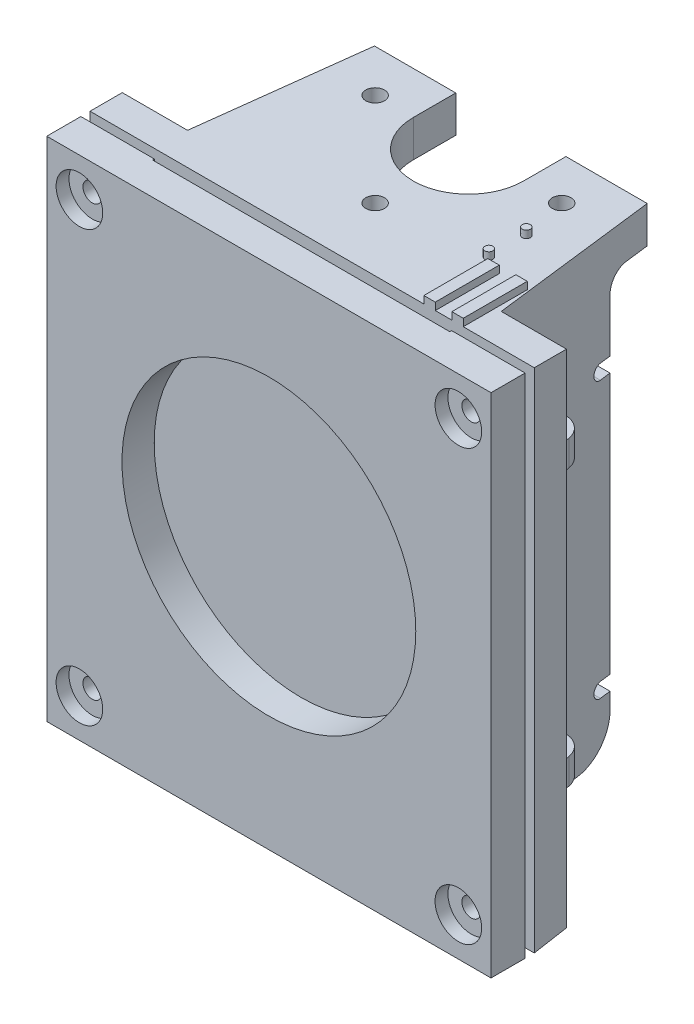
SolidWorks part; units mm, degrees
ref_plane "Front Plane" through (0, 0, 0) normal (0, 0, 1) x (1, 0, 0)
ref_plane "Top Plane" through (0, 0, 0) normal (0, 1, 0) x (1, 0, 0)
ref_plane "Right Plane" through (0, 0, 0) normal (1, 0, 0) x (0, 0, -1)
sketch "Sketch1" plane through (0, 0, 0) normal (0, 1, 0) x (1, 0, 0)
  line L0 (-32.5572, 0) -> (-38.5572, 0)
  line L5 (-38.5572, 0) -> (-42.7047, -33.7788)
  line L7 (42.7047, -33.7788) -> (38.5572, 0)
  line L8 (38.5572, 0) -> (32.5572, 0)
  line L9 (-42.7047, -33.7788) -> (-60.4847, -33.7788)
  line L10 (-60.4847, -33.7788) -> (-60.4847, -42.5572)
  line L11 (-60.4847, -42.5572) -> (60.4847, -42.5572)
  line L12 (60.4847, -42.5572) -> (60.4847, -33.7788)
  line L13 (60.4847, -33.7788) -> (42.7047, -33.7788)
  line L14 (0, 0) -> (0, -32.5572) construction
  line L15 (38.5572, 0) -> (38.5572, -26.0046) construction
  line L16 (51.5947, -33.7788) -> (51.5947, -54.3356) construction
  line L17 (-60.4847, -45.5572) -> (60.4847, -45.5572)
  line L18 (-60.4847, -45.5572) -> (-60.4847, -54.3356)
  line L19 (-60.4847, -54.3356) -> (60.4847, -54.3356)
  line L20 (60.4847, -45.5572) -> (60.4847, -54.3356)
  line L21 (49.042, -33.7788) -> (49.042, -54.3356) construction
  line L23 (54.1474, -33.7788) -> (54.1474, -54.3356) construction
  line L26 (46.8322, -36.9538) -> (56.3572, -36.9538) construction
  line L27 (46.8322, -36.9538) -> (46.8322, -33.7788) construction
  line L28 (46.8322, -33.7788) -> (56.3572, -33.7788) construction
  line L29 (56.3572, -36.9538) -> (56.3572, -33.7788) construction
  line L30 (46.8322, -36.9538) -> (56.3572, -33.7788) construction
  line L31 (46.8322, -33.7788) -> (56.3572, -36.9538) construction
  line L32 (49.9992, -31.7788) -> (74.4903, -31.7788) construction
  line L33 (45.2447, -55.9088) -> (57.9447, -55.9088) construction
  line L34 (45.2447, -55.9088) -> (45.2447, -50.8288) construction
  line L35 (45.2447, -50.8288) -> (57.9447, -50.8288) construction
  line L36 (57.9447, -55.9088) -> (57.9447, -50.8288) construction
  line L37 (45.2447, -55.9088) -> (57.9447, -50.8288) construction
  line L38 (45.2447, -50.8288) -> (57.9447, -55.9088) construction
  circle A0 centre (0, 0) radius 32.5572 construction
  arc A1 (-32.5572, 0) -> (32.5572, 0) centre (0, 0) ccw
  point P27 (51.5947, -35.3663)
  point P32 (51.5947, -53.3688)
  point P44 (42.7047, -33.7788)
  point P47 (-42.7047, -33.7788)
  dimension "D1" = 65.1144
  dimension "D2" = 10
  dimension "D3" = 6
  dimension "D4" = 7
  dimension "D6" = 3
  dimension "D5" = 5.1054
  dimension "D7" = 9.525
  dimension "D8" = 3.175
  dimension "D9" = 2
  dimension "D11" = 12.7
  dimension "D12" = 5.08
  dimension "D13" = 2.54
  dimension "D10" = 19.05
  dimension "D14" = 5.6034
extrude "Boss-Extrude1" add sketch "Sketch1" along normal mid plane 113.03 contours A1 L8 L7 L13 L12 L11 L10 L9 L5 L0
sketch "Sketch4" plane through (0, -56.515, 0) normal (0, -1, 0) x (1, 0, 0)
  line L0 (-60.4847, 33.7788) -> (-60.4847, 42.5572) construction
  line L1 (60.4847, 42.5572) -> (-60.4847, 42.5572)
  line L2 (60.4847, 42.5572) -> (60.4847, 33.7788)
  line L4 (-60.4847, 42.5572) -> (-60.4847, 33.7788)
  line L5 (60.4847, 33.7788) -> (42.7047, 33.7788)
  line L6 (42.7047, 33.7788) -> (38.5572, 0) construction
  line L7 (42.7047, 33.7788) -> (40.399, 15)
  line L8 (40.399, 15) -> (-40.399, 15) construction
  line L9 (-38.5572, 0) -> (-42.7047, 33.7788) construction
  line L10 (-40.399, 15) -> (-42.7047, 33.7788)
  line L11 (-42.7047, 33.7788) -> (-60.4847, 33.7788)
  line L12 (40.399, 15) -> (13.2288, 15)
  line L13 (-40.399, 15) -> (-13.2288, 15)
  line L14 (-42.7047, 33.7788) -> (-60.4847, 33.7788) construction
  circle A0 centre (0, 0) radius 20 construction
  arc A1 (13.2288, 15) -> (-13.2288, 15) centre (0, 0) ccw
  arc A2 (32.5572, 0) -> (-32.5572, 0) centre (0, 0) ccw construction
  dimension "D2" = 40
  dimension "D3" = 15
extrude "Boss-Extrude2" add sketch "Sketch4" along normal blind 15
sketch "Sketch5" plane through (0, 56.515, 0) normal (0, 1, 0) x (1, 0, 0)
  line L0 (-42.7047, -33.7788) -> (-37.1387, 11.5527)
  line L1 (-60.4847, -42.5572) -> (60.4847, -42.5572)
  line L2 (-60.4847, -42.5572) -> (-60.4847, -33.7788)
  line L3 (-60.4847, -33.7788) -> (60.4847, -33.7788) construction
  line L4 (60.4847, -42.5572) -> (60.4847, -33.7788)
  line L5 (-37.1387, 11.5527) -> (-15, 11.5527)
  line L6 (37.1387, 11.5527) -> (42.7047, -33.7788)
  line L7 (-42.7047, -33.7788) -> (-60.4847, -33.7788) construction
  line L8 (42.7047, -33.7788) -> (38.5572, 0) construction
  line L9 (-38.5572, 0) -> (-42.7047, -33.7788) construction
  line L10 (-60.4847, -33.7788) -> (-42.7047, -33.7788)
  line L11 (42.7047, -33.7788) -> (60.4847, -33.7788)
  line L12 (-15, 11.5527) -> (-15, 0)
  line L13 (15, 11.5527) -> (15, 0)
  line L14 (15, 11.5527) -> (37.1387, 11.5527)
  line L15 (60.4847, -42.5572) -> (60.4847, -33.7788) construction
  circle A0 centre (0, 0) radius 25.4 construction
  circle A1 centre (0, -25.4) radius 2.5527
  circle A2 centre (25.4, 0) radius 2.5527
  circle A3 centre (-25.4, 0) radius 2.5527
  arc A4 (-15, 0) -> (15, 0) centre (0, 0) ccw
  dimension "D1" = 50.8
  dimension "D2" = 5.1054
  dimension "D3" = 15
  dimension "D4" = 9
extrude "Boss-Extrude3" add sketch "Sketch5" along normal blind 10
sketch "Sketch7" plane through (0, 0, 33.7788) normal (0, 0, -1) x (-1, 0, 0)
  line L0 (51.5947, 66.515) -> (51.5947, -71.515) construction
  line L1 (42.7047, 66.515) -> (60.4847, 66.515) construction
  line L2 (60.4847, -71.515) -> (42.7047, -71.515) construction
  line L3 (60.4847, -2.5) -> (-60.4847, -2.5) construction
  line L4 (60.4847, 66.515) -> (60.4847, -71.515) construction
  line L5 (-60.4847, 66.515) -> (-60.4847, -71.515) construction
  line L6 (46.8322, -58.2661) -> (51.5947, -55.5165)
  line L7 (51.5947, 50.5165) -> (56.3572, 53.2661)
  line L8 (56.3572, 53.2661) -> (56.3572, 58.7654)
  line L9 (56.3572, 58.7654) -> (51.5947, 61.515)
  line L10 (51.5947, 61.515) -> (46.8322, 58.7654)
  line L11 (46.8322, 58.7654) -> (46.8322, 53.2661)
  line L12 (46.8322, 53.2661) -> (51.5947, 50.5165)
  line L13 (46.8322, -63.7654) -> (46.8322, -58.2661)
  line L14 (51.5947, -66.515) -> (46.8322, -63.7654)
  line L15 (56.3572, -63.7654) -> (51.5947, -66.515)
  line L16 (56.3572, -58.2661) -> (56.3572, -63.7654)
  line L17 (51.5947, -55.5165) -> (56.3572, -58.2661)
  line L18 (0, 0) -> (0, -85.6539) construction
  line L19 (-51.5947, -55.5165) -> (-56.3572, -58.2661)
  line L20 (-56.3572, -58.2661) -> (-56.3572, -63.7654)
  line L21 (-56.3572, -63.7654) -> (-51.5947, -66.515)
  line L22 (-51.5947, -66.515) -> (-46.8322, -63.7654)
  line L23 (-46.8322, -63.7654) -> (-46.8322, -58.2661)
  line L24 (-46.8322, 53.2661) -> (-51.5947, 50.5165)
  line L25 (-46.8322, 58.7654) -> (-46.8322, 53.2661)
  line L26 (-51.5947, 61.515) -> (-46.8322, 58.7654)
  line L27 (-56.3572, 58.7654) -> (-51.5947, 61.515)
  line L28 (-56.3572, 53.2661) -> (-56.3572, 58.7654)
  line L29 (-51.5947, 50.5165) -> (-56.3572, 53.2661)
  line L30 (-46.8322, -58.2661) -> (-51.5947, -55.5165)
  circle A0 centre (51.5947, 56.0157) radius 4.7625 construction
  circle A1 centre (51.5947, -61.0157) radius 4.7625 construction
  circle A2 centre (-51.5947, -61.0157) radius 4.7625 construction
  circle A3 centre (-51.5947, 56.0157) radius 4.7625 construction
  dimension "D1" = 9.525
  dimension "D2" = 5
ref_plane "Plane1" through (0, 0, 36.9538) normal (0, 0, -1) x (-1, 0, 0)
extrude "Cut-Extrude1" cut sketch "Sketch7" against normal up to surface (3.175 mm away) up to plane "Plane1"
sketch "Sketch9" plane through (0, 0, 33.7788) normal (0, 0, -1) x (-1, 0, 0)
  circle A0 centre (51.5947, 56.0157) radius 2.5527
  circle A1 centre (51.5947, -61.0157) radius 2.5527
  circle A2 centre (-51.5947, -61.0157) radius 2.5527
  circle A3 centre (-51.5947, 56.0157) radius 2.5527
  dimension "D1" = 5.1054
extrude "Cut-Extrude2" cut sketch "Sketch9" against normal up to next
extrude "Boss-Extrude4" add sketch "Sketch1<3>" along normal up to surface and the other way up to surface separate body contours L19 L20 L17 L18 up to face at (25.4, 66.515, 2.5527) other way up to face at (0, -71.515, 28.523)
sketch "Sketch1<3>" plane through (0, 0, 0) normal (0, 1, 0) x (1, 0, 0) same geometry as "Sketch1"
sketch "Sketch10" plane through (0, 0, 54.3356) normal (0, 0, 1) x (1, 0, 0)
  circle A0 centre (-51.5947, 56.0157) radius 6.35
  circle A1 centre (51.5947, 56.0157) radius 6.35
  circle A2 centre (51.5947, -61.0157) radius 6.35
  circle A3 centre (-51.5947, -61.0157) radius 6.35
  dimension "D1" = 12.7
extrude "Cut-Extrude3" cut sketch "Sketch10" against normal up to vertex (3.5067 mm away) up to point (57.9447, 0, 50.8288)
sketch "Sketch11" plane through (0, 66.515, 0) normal (0, 1, 0) x (1, 0, 0)
  line L0 (-60.4847, -45.5572) -> (-60.4847, -45.0572)
  line L1 (-60.4847, -45.0572) -> (-40.4847, -45.0572)
  line L2 (-40.4847, -45.0572) -> (-40.4847, -45.5572)
  line L3 (-60.4847, -45.5572) -> (60.4847, -45.5572) construction
  line L4 (-40.4847, -45.5572) -> (-60.4847, -45.5572)
  line L5 (0, -45.5572) -> (0, -54.3356) construction
  line L6 (-60.4847, -54.3356) -> (60.4847, -54.3356) construction
  line L7 (40.4847, -45.5572) -> (60.4847, -45.5572)
  line L8 (40.4847, -45.0572) -> (40.4847, -45.5572)
  line L9 (60.4847, -45.0572) -> (40.4847, -45.0572)
  line L10 (60.4847, -45.5572) -> (60.4847, -45.0572)
  dimension "D1" = 0.5
  dimension "D2" = 20
extrude "Boss-Extrude5" add sketch "Sketch11" against normal up to surface (138.03 mm away) up to face at (0, -71.515, 49.9464)
extrude "Cut-Extrude4" cut sketch "Sketch9<2>" against normal through all both and the other way through all contours A1 | A2 | A3 | A0
sketch "Sketch9<2>" plane through (0, 0, 33.7788) normal (0, 0, -1) x (-1, 0, 0) same geometry as "Sketch9"
ref_plane "Plane2" through (0, -36.515, 0) normal (0, -1, 0) x (-1, 0, 0)
sketch "Sketch13" plane through (0, -36.515, 0) normal (0, -1, 0) x (-1, 0, 0)
  line L0 (0, 0) -> (0, -54.3356) construction
  line L1 (60.4847, -54.3356) -> (-60.4847, -54.3356) construction
  line L2 (-53.8496, -26.5153) -> (-56.6783, -42.5572)
  line L3 (-56.6783, -42.5572) -> (-41.9408, -42.5572)
  line L4 (-60.4847, -42.5572) -> (60.4847, -42.5572) construction
  line L5 (-41.9408, -42.5572) -> (-41.9408, -27.5572)
  line L7 (-40.399, -15) -> (-42.7047, -33.7788) construction
  circle A0 centre (-47.9408, -27.5572) radius 6 construction
  circle A1 centre (-47.9408, -27.5572) radius 2
  arc A2 (-53.8496, -26.5153) -> (-41.9408, -27.5572) centre (-47.9408, -27.5572) cw
  point P0 (-55.9726, -42.5572)
  dimension "D1" = 4
  dimension "D2" = 6
  dimension "D3" = 15
  dimension "D4" = 10
extrude "Boss-Extrude6" add sketch "Sketch13" along normal blind 7
mirror "Mirror1" about plane through (0, 0, 0) normal (1, 0, 0) of "Boss-Extrude6"
ref_plane "Plane3" through (0, -2.5, 0) normal (0, -1, 0) x (-1, 0, 0)
draft "Draft1" type of draft neutral plane draft angle 10 faces to draft 1 face at (0, -71.515, 28.523) neutral plane through (-60.4847, 56.515, 42.5572) neutral plane normal (0, 0, 1) reverse direction yes parameters "D1"=10
fillet "Fillet5" radius 1.3 4 edges at (-54.1474, 56.0157, 36.9538) (49.042, 56.0157, 36.9538) (49.042, -61.0157, 36.9538) (-54.1474, -61.0157, 36.9538)
sketch "Sketch16" plane through (0, 0, 54.3356) normal (0, 0, 1) x (1, 0, 0)
  circle A0 centre (0, 0) radius 40
  dimension "D1" = 80
extrude "Cut-Extrude6" cut sketch "Sketch16" against normal up to next (8.7784 mm away)
mirror "Mirror2" about plane through (0, -2.5, 0) normal (0, -1, 0) of "Boss-Extrude6", "Mirror1"
fillet "Fillet6" radius 5 4 edges at (41.9408, 35.015, 27.5572) (41.9408, -40.015, 27.5572) (-41.9408, -40.015, 27.5572) (-41.9408, 35.015, 27.5572)
fillet "Fillet7" radius 5 4 edges at (-55.1304, 35.015, 33.7788) (-55.1304, -40.015, 33.7788) (55.1304, 35.015, 33.7788) (55.1304, -40.015, 33.7788)
sketch "Sketch17" plane through (60.4847, 0, 0) normal (1, 0, 0) x (0, 0, -1)
  line L0 (0, -40.015) -> (-3, -40.015) construction
  line L1 (0, 56.515) -> (0, -56.515) construction
  line L2 (0, -42.015) -> (-3, -42.015)
  line L3 (0, -38.015) -> (-3, -38.015)
  line L4 (-3, -40.015) -> (-17.4062, -40.015) construction
  line L5 (-17.4062, -36.515) -> (-17.4062, -43.515) construction
  line L6 (-33.7788, -2.5) -> (15.3847, -2.5) construction
  line L9 (-33.7788, 31.515) -> (-33.7788, -36.515) construction
  line L10 (0, 35.015) -> (-3, 35.015) construction
  line L11 (0, 37.015) -> (-3, 37.015)
  line L12 (0, 33.015) -> (-3, 33.015)
  arc A0 (0, -42.015) -> (0, -38.015) centre (0, -40.015) ccw
  arc A1 (-3, -38.015) -> (-3, -42.015) centre (-3, -40.015) ccw
  arc A2 (0, 37.015) -> (0, 33.015) centre (0, 35.015) cw
  arc A3 (-3, 33.015) -> (-3, 37.015) centre (-3, 35.015) cw
  point P4 (-1.5, -40.015)
  point P19 (-1.5, 35.015)
  dimension "D2" = 2
  dimension "D1" = 3
extrude "Cut-Extrude7" cut sketch "Sketch17" against normal through all both and the other way through all
fillet "Fillet8" radius 5 2 edges at (-35.5572, 56.515, 0) (35.5572, 56.515, 0)
fillet "Fillet10" radius 10 2 edges at (-35.5572, -56.515, 0) (35.5572, -56.515, 0)
fillet "Fillet12" radius 3 2 edges at (-34.6474, -56.515, 15) (34.6474, -56.515, 15)
fillet "Fillet13" radius 3 8 edges at (32.5572, -44.265, 0) (29.3934, -57.279, 14) (30.6405, -56.515, 11.0059) (-29.1727, -57.7897, 14.4543) (-30.6405, -56.515, 11.0059) (-32.5572, -44.265, 0) (32.4836, -52.7572, 2.1875) (-32.3245, -54.4282, 3.886)
sketch "Sketch19" plane through (0, 66.515, 0) normal (0, 1, 0) x (1, 0, 0)
  line L0 (-60.4847, -42.5572) -> (60.4847, -42.5572) construction
  line L1 (25.6272, -9.928) -> (44.2272, -9.928) construction
  line L2 (25.6272, -9.928) -> (25.6272, -25.128) construction
  line L3 (25.6272, -25.128) -> (44.2272, -25.128) construction
  line L4 (44.2272, -9.928) -> (44.2272, -25.128) construction
  line L5 (30.4255, -42.5572) -> (33.5315, -42.5572)
  line L6 (30.4255, -42.5572) -> (30.4255, -25.128)
  line L7 (30.4255, -25.128) -> (33.5315, -25.128)
  line L8 (33.5315, -42.5572) -> (33.5315, -25.128)
  line L9 (34.9272, -9.928) -> (34.9272, -25.128) construction
  line L10 (38.0442, -25.128) -> (41.1502, -25.128)
  line L11 (38.0442, -25.128) -> (38.0442, -42.5572)
  line L12 (38.0442, -42.5572) -> (41.1502, -42.5572)
  line L13 (41.1502, -25.128) -> (41.1502, -42.5572)
  line L14 (25.6272, -17.528) -> (44.2272, -17.528) construction
  circle A0 centre (28.1985, -12.428) radius 1.1
  circle A1 centre (28.1985, -22.628) radius 1.1
  point P22 (40.4836, -25.7367)
  point P23 (41.1502, -25.832)
  point P24 (33.5315, -25.832)
  point P25 (27.0557, -25.1653)
  point P29 (28.1985, -12.3088)
  point P30 (25.6272, -9.928)
  dimension "D3" = 2.2
  dimension "D1" = 18.6
  dimension "D2" = 15.2
  dimension "D4" = 10.2
extrude "Boss-Extrude7" add sketch "Sketch19" along normal blind 2
equation "\"D1@Sketch1\"=2.536in+0.7mm"
equation "\"D5@Sketch1\"=0.201in"
equation "\"D7@Sketch1\"=0.375in"
equation "\"D6@Sketch1\"=3mm"
equation "\"D10@Sketch1\"=0.75in"
equation "\"D1@Boss-Extrude1\"=4.45in"
equation "\"D1@Sketch5\"=2in"
equation "\"D2@Sketch5\"=0.201in"
equation "\"D1@Sketch7\"=0.375in"
equation "\"D1@Sketch9\"=0.201in"
equation "\"D1@Sketch10\"=12.7"
